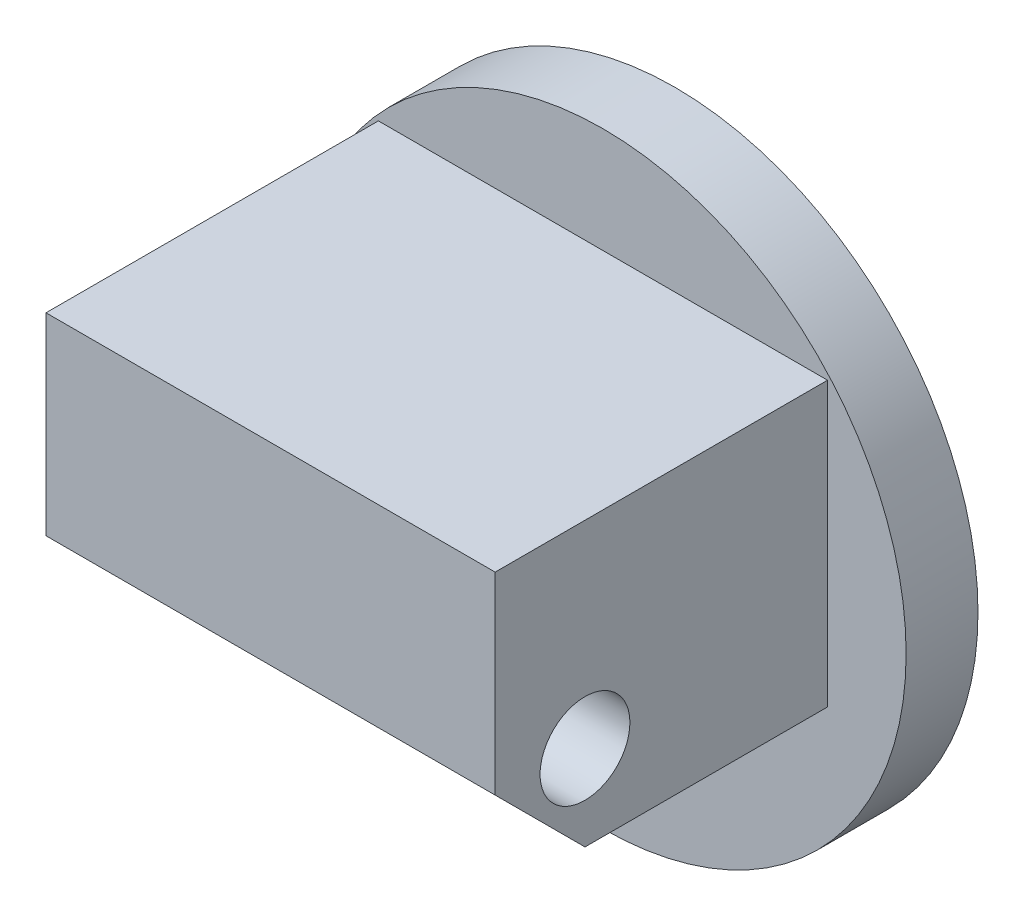
SolidWorks part; units mm, degrees
ref_plane "Front Plane" through (0, 0, 0) normal (0, 0, 1) x (1, 0, 0)
ref_plane "Top Plane" through (0, 0, 0) normal (0, 1, 0) x (1, 0, 0)
ref_plane "Right Plane" through (0, 0, 0) normal (1, 0, 0) x (0, 0, -1)
sketch "Sketch1" plane through (0, 0, 0) normal (0, 0, 1) x (1, 0, 0)
  circle A0 centre (0, 0) radius 6.75
  dimension "D1" = 13.5
extrude "Boss-Extrude1" add sketch "Sketch1" along normal blind 9
sketch "Sketch2" plane through (0, 0, 0) normal (0, 0, -1) x (-1, 0, 0)
  circle A0 centre (0, 0) radius 5
  dimension "D1" = 10
extrude "Boss-Extrude2" add sketch "Sketch2" along normal blind 1
sketch "Sketch3" plane through (0, 0, 0) normal (0, 1, 0) x (1, 0, 0)
  line L0 (0, 0) -> (0, -9) construction
  line L1 (-6.75, -9) -> (6.75, -9) construction
  line L2 (-6.75, 0) -> (-6.75, -9) construction
  line L3 (-6.75, -1.6) -> (-5, -1.6)
  line L4 (-6.75, -1.6) -> (-6.75, -9)
  line L5 (-6.75, -9) -> (-5, -9)
  line L6 (-5, -1.6) -> (-5, -9)
  line L7 (6.75, 0) -> (-6.75, 0) construction
  line L8 (5, -1.6) -> (5, -9)
  line L9 (6.75, -9) -> (5, -9)
  line L10 (6.75, -1.6) -> (6.75, -9)
  line L11 (6.75, -1.6) -> (5, -1.6)
  dimension "D1" = 1.6
  dimension "D2" = 10
extrude "Cut-Extrude1" cut sketch "Sketch3" against normal through all both and the other way through all
sketch "Sketch4" plane through (0, 0, 0) normal (1, 0, 0) x (0, 0, -1)
  line L0 (-9, 4.5346) -> (-9, -4.5346) construction
  line L1 (-9, 4.4) -> (-1.6, 4.4)
  line L2 (-9, 4.4) -> (-9, -1.9)
  line L3 (-9, -1.9) -> (-1.6, -1.9)
  line L4 (-1.6, 4.4) -> (-1.6, -1.9)
  line L5 (-1.6, 4.5346) -> (-1.6, -4.5346) construction
  line L6 (-9, -6.75) -> (0, -6.75) construction
  line L7 (0, 6.75) -> (-9, 6.75) construction
  line L8 (-9, -1.9) -> (-1.6, -1.9)
  line L9 (-9, -1.9) -> (-9, -6.75)
  line L10 (-9, -6.75) -> (-1.6, -6.75)
  line L11 (-1.6, -1.9) -> (-1.6, -6.75)
  line L12 (-9, 4.4) -> (-1.6, 4.4)
  line L13 (-9, 4.4) -> (-9, 6.75)
  line L14 (-9, 6.75) -> (-1.6, 6.75)
  line L15 (-1.6, 4.4) -> (-1.6, 6.75)
  dimension "D1" = 6.3
  dimension "D2" = 4.85
extrude "Cut-Extrude2" cut sketch "Sketch4" against normal through all both and the other way through all contours L11 L3 L9 L10 | L1 L15 L14 L13 region at (0, 5.575, 5.3) region at (0, -4.325, 5.3)
sketch "Sketch5" plane through (5, 0, 0) normal (1, 0, 0) x (0, 0, -1)
  circle A0 centre (-7, 0) radius 1
  dimension "D2" = 2
  dimension "D1" = 7
extrude "Cut-Extrude3" cut sketch "Sketch5" against normal through all both
chamfer "Chamfer1" distance 2 1 edges at (0, -1.9, 9)
